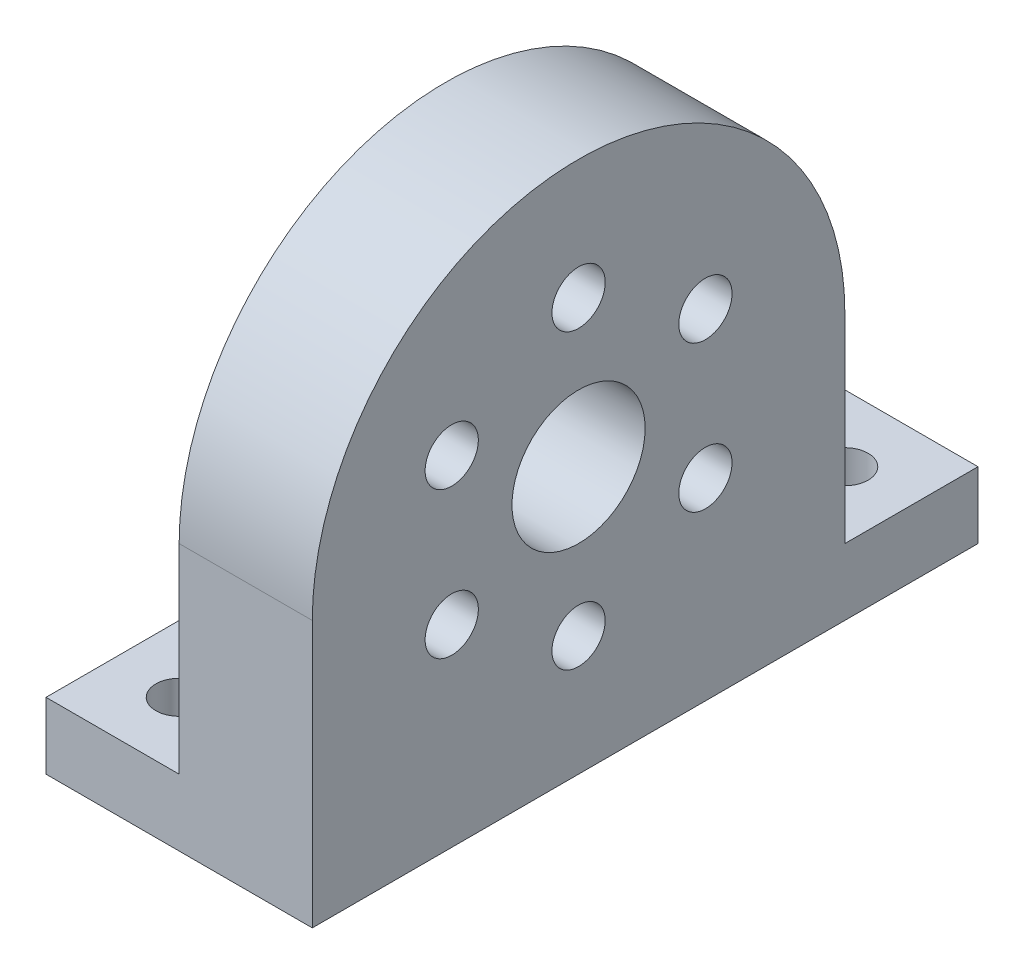
SolidWorks part; units mm, degrees
ref_plane "Front Plane" through (0, 0, 0) normal (0, 0, 1) x (1, 0, 0)
ref_plane "Top Plane" through (0, 0, 0) normal (0, 1, 0) x (1, 0, 0)
ref_plane "Right Plane" through (0, 0, 0) normal (1, 0, 0) x (0, 0, -1)
sketch "Sketch1" plane through (0, 0, 0) normal (1, 0, 0) x (0, 0, -1)
  line L0 (20, -15) -> (30, -15)
  line L1 (-30, -20) -> (30, -20)
  line L2 (-30, -20) -> (-30, -15)
  line L3 (-30, -15) -> (-20, -15)
  line L4 (30, -20) -> (30, -15)
  line L6 (-20, 0) -> (-20, -15)
  line L7 (-22.3599, -20) -> (-15.8566, -20)
  line L10 (20, 0) -> (20, -15)
  line L11 (17.6401, -20) -> (9.951, -20)
  line L12 (-20, -15) -> (-20, -20)
  circle A1 centre (0, 11) radius 2
  circle A2 centre (9.5263, 5.5) radius 2
  circle A3 centre (9.5263, -5.5) radius 2
  circle A4 centre (0, -11) radius 2
  circle A5 centre (-9.5263, -5.5) radius 2
  circle A6 centre (-9.5263, 5.5) radius 2
  arc A7 (20, 0) -> (-20, 0) centre (0, 0) ccw
  circle A8 centre (0, 0) radius 5
  point P18 (0, 0)
  dimension "D1" = 4
  dimension "D2" = 10
  dimension "D5" = 20
  dimension "D11" = 9.951
  dimension "D3" = 11
  dimension "D6" = 30
  dimension "D7" = 30
  dimension "D8" = 5
  dimension "D9" = 10
  dimension "D10" = 20
  dimension "D12" = 17.6401
  dimension "D13" = 15.8566
  dimension "D14" = 22.3599
  dimension "D4" = 6
extrude "Boss-Extrude1" add sketch "Sketch1" along normal blind 10 contours L10 A7 L6 L3 L2 L1 L4 L0 A8 A1 A2 A3 A4 A5 A6 region at (0, -15.6403, -25)
hole_wizard "CSK for M3 Flat Head Machine Screw1" positions "Sketch3" profile "Sketch4" countersink size "M3" standard "ANSI Metric" end condition through all
sketch "Sketch3" plane through (0, 0, 0) normal (-1, 0, 0) x (0, 0, 1)
  point P0 (0, 11)
  point P3 (9.5263, 5.5)
  point P6 (9.5263, -5.5)
  point P9 (0, -11)
  point P12 (-9.5263, -5.5)
  point P15 (-9.5263, 5.5)
sketch "Sketch4" plane through (0, 11, 0) normal (0, 1, 0) x (0, 0, 1)
  line L0 (0, 0) -> (0, 10)
  line L1 (0, 10) -> (1.7, 10)
  line L2 (1.7, 10) -> (1.7, 1.45)
  line L3 (1.7, 1.45) -> (3.15, 0)
  line L5 (3.15, 0) -> (0, 0)
  line L6 (-1.7, 1.45) -> (-3.15, 0) construction
  line L11 (0, -6.35) -> (0, 107.95) construction
  dimension "Thru Hole Dia." = 3.4
  dimension "Thru Hole Depth" = 10
  dimension "Near C'Sink Dia." = 6.3
  dimension "Near C'Sink Angle" = 90
sketch "Sketch6" plane through (0, -20, 0) normal (0, -1, 0) x (1, 0, 0)
  line L0 (0, 20) -> (-10, 20)
  line L1 (-10, 20) -> (-10, 10)
  line L2 (-10, 10) -> (0, 10)
  line L3 (0, 20) -> (0, -30) construction
  line L4 (0, 20) -> (10, 20)
  line L5 (10, 20) -> (10, 10)
  line L6 (10, 20) -> (10, -30) construction
  line L7 (10, 10) -> (0, 10)
  dimension "D1" = 10
  dimension "D2" = 10
extrude "Boss-Extrude2" add sketch "Sketch6" against normal blind 5
hole_wizard "Ø3.0mm Dowel Hole1" positions "3DSketch1" profile "Sketch7" hole size "Ø3.0" standard "ANSI Metric"
sketch3d "3DSketch1"
  line L5 (0, -15, 20) -> (-10, -15, 20) construction
  line L6 (-10, -15, 20) -> (-10, -15, 10) construction
  line L7 (10, -15, -20) -> (10, -15, -30) construction
  line L8 (10, -15, -30) -> (0, -15, -30) construction
  point P0 (5, -15, -25)
  point P2 (-5, -15, 15)
  dimension "D1" = 5
  dimension "D2" = 5
  dimension "D3" = 5
  dimension "D4" = 5
sketch "Sketch7" plane through (5, -15, -25) normal (1, 0, 0) x (0, 0, 1)
  line L0 (0, 0) -> (0, 5)
  line L1 (0, 5) -> (1.75, 5)
  line L2 (1.75, 5) -> (1.75, 0)
  line L5 (1.75, 0) -> (0, 0)
  line L10 (0, 5) -> (-1.75, 5) construction
  line L11 (0, -6.35) -> (0, 107.95) construction
  dimension "Hole Dia." = 3.5
  dimension "Hole Depth" = 5
  dimension "Drill Angle" = 180
